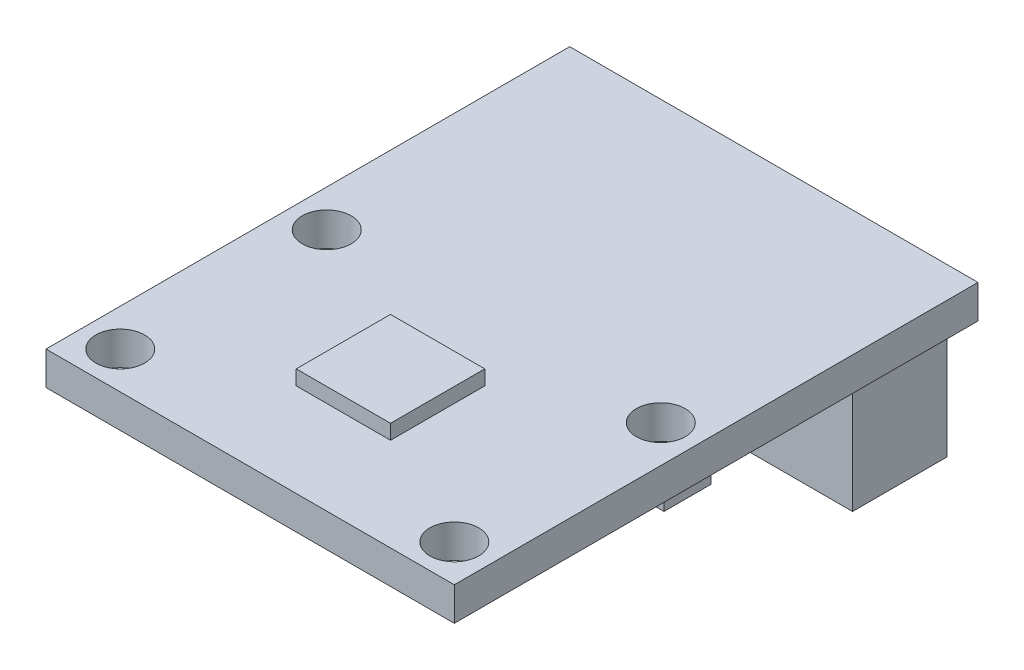
SolidWorks part; units mm, degrees
ref_plane "Front Plane" through (0, 0, 0) normal (0, 0, 1) x (1, 0, 0)
ref_plane "Top Plane" through (0, 0, 0) normal (0, 1, 0) x (1, 0, 0)
ref_plane "Right Plane" through (0, 0, 0) normal (1, 0, 0) x (0, 0, -1)
sketch "Sketch1" plane through (0, 0, 0) normal (0, 1, 0) x (1, 0, 0)
  line L0 (-9, -5.5625) -> (-11, -7.5625) construction
  line L9 (-9, 5.5625) -> (9, -5.5625) construction
  line L11 (-9, 5.5625) -> (9, 5.5625) construction
  line L12 (-9, 5.5625) -> (-9, -5.5625) construction
  line L13 (-9, -5.5625) -> (9, -5.5625) construction
  line L14 (9, 5.5625) -> (9, -5.5625) construction
  line L15 (9, -5.5625) -> (11, -7.5625) construction
  line L17 (-11, -7.5625) -> (11, -7.5625)
  line L18 (-11, -7.5625) -> (-11, 20.6542)
  line L19 (-11, 20.6542) -> (11, 20.6542)
  line L20 (11, -7.5625) -> (11, 20.6542)
  line L21 (-11, -7.5625) -> (11, 20.6542) construction
  line L22 (-11, 20.6542) -> (11, -7.5625) construction
  circle A0 centre (-9, 5.5625) radius 1.315
  circle A1 centre (9, 5.5625) radius 1.315
  circle A2 centre (9, -5.5625) radius 1.315
  circle A3 centre (-9, -5.5625) radius 1.315
  point P0 (0, 6.5458)
  point P1 (-10.0081, -7.2507)
  point P3 (0, 6.5458)
  point P4 (0, 0)
  point P5 (0, 5.093)
  point P8 (11, -9.2659)
  point P16 (0, 0)
  dimension "D3" = 2.63
  dimension "D1" = 28.2167
  dimension "D4" = 18
  dimension "D5" = 11.125
  dimension "D6" = 22
extrude "Boss-Extrude1" add sketch "Sketch1" along normal blind 1.8
sketch "Sketch2" plane through (0, 1.8, 0) normal (0, 1, 0) x (1, 0, 0)
  line L10 (-2.54, -2.54) -> (2.54, -2.54)
  line L11 (-2.54, -2.54) -> (-2.54, 2.54)
  line L12 (-2.54, 2.54) -> (2.54, 2.54)
  line L13 (2.54, -2.54) -> (2.54, 2.54)
  line L14 (-2.54, -2.54) -> (2.54, 2.54) construction
  line L15 (-2.54, 2.54) -> (2.54, -2.54) construction
  point P0 (0, 0)
  dimension "D1" = 5.08
extrude "Boss-Extrude2" add sketch "Sketch2" along normal blind 0.7937
sketch "Sketch3" plane through (0, 0, 0) normal (0, -1, 0) x (-1, 0, 0)
  line L0 (-11, 20.6542) -> (-10.16, 19.8142) construction
  line L1 (-5.08, 12.1942) -> (2.54, 12.1942)
  line L2 (-5.08, 12.1942) -> (-5.08, 9.6542)
  line L3 (-5.08, 9.6542) -> (2.54, 9.6542)
  line L4 (2.54, 12.1942) -> (2.54, 9.6542)
  line L5 (-5.08, 12.1942) -> (2.54, 9.6542) construction
  line L6 (-5.08, 9.6542) -> (2.54, 12.1942) construction
  line L7 (-10.16, 19.8142) -> (10.16, 19.8142)
  line L8 (-10.16, 19.8142) -> (-10.16, 14.7342)
  line L9 (-10.16, 14.7342) -> (10.16, 14.7342)
  line L10 (10.16, 19.8142) -> (10.16, 14.7342)
  line L11 (-10.16, 19.8142) -> (10.16, 14.7342) construction
  line L12 (-10.16, 14.7342) -> (10.16, 19.8142) construction
  line L13 (10.16, 19.8142) -> (11, 20.6542) construction
  point P4 (-1.27, 10.9242)
  point P9 (0, 17.2742)
  point P10 (11, 20.6542)
  point P19 (-11, 20.6542)
  dimension "D1" = 20.32
  dimension "D2" = 5.08
  dimension "D3" = 2.54
  dimension "D4" = 7.62
  dimension "D5" = 1.27
  dimension "D6" = 2.54
extrude "Boss-Extrude3" add sketch "Sketch3" along normal blind 6.35
equation "\"PINWIDTH\"= .1"
equation "\"D1@Sketch3\"=\"PINWIDTH\"*8"
equation "\"D2@Sketch3\"=\"PINWIDTH\"*2"
equation "\"D3@Sketch3\"=\"PINWIDTH\""
equation "\"D4@Sketch3\"=\"PINWIDTH\"*3"
equation "\"D5@Sketch3\"=\"PINWIDTH\"*.5"
